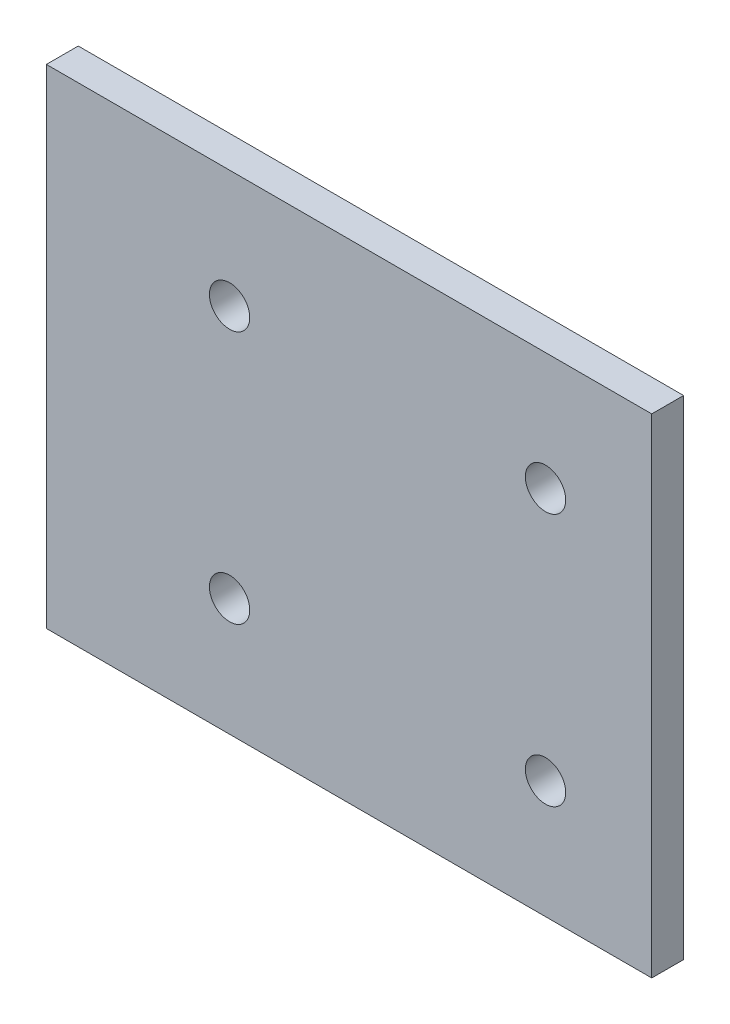
SolidWorks part; units mm, degrees
material "Oak"
ref_plane "Front Plane" through (0, 0, 0) normal (0, 0, 1) x (1, 0, 0)
ref_plane "Top Plane" through (0, 0, 0) normal (0, 1, 0) x (1, 0, 0)
ref_plane "Right Plane" through (0, 0, 0) normal (1, 0, 0) x (0, 0, -1)
sketch "Sketch1" plane through (0, 0, 0) normal (0, 0, 1) x (1, 0, 0)
  line L1 (-36.0143, 24.5902) -> (20.9857, 24.5902)
  line L2 (-36.0143, 24.5902) -> (-36.0143, -21.4098)
  line L3 (-36.0143, -21.4098) -> (20.9857, -21.4098)
  line L4 (20.9857, 24.5902) -> (20.9857, -21.4098)
  dimension "D1" = 46
  dimension "D2" = 57
extrude "Boss-Extrude1" add sketch "Sketch1" along normal blind 3
hole_wizard "#6 Clearance Hole1" positions "Sketch2" profile "Sketch3" hole size "#6" standard "ANSI Inch" end condition through all
sketch "Sketch2" plane through (0, 0, 3) normal (0, 0, 1) x (1, 0, 0)
  line L0 (20.9857, -21.4098) -> (20.9857, 24.5902) construction
  line L1 (20.9857, 24.5902) -> (-36.0143, 24.5902) construction
  line L2 (-36.0143, -21.4098) -> (20.9857, -21.4098) construction
  point P0 (10.9857, 13.5152)
  point P2 (10.9857, -10.3348)
  point P4 (-18.7643, -10.3348)
  point P6 (-18.7643, 13.5152)
  dimension "D1" = 29.75
  dimension "D2" = 29.75
  dimension "D3" = 23.85
  dimension "D4" = 23.85
  dimension "D5" = 10
  dimension "D6" = 11.075
  dimension "D7" = 10
  dimension "D8" = 11.075
sketch "Sketch3" plane through (10.9857, 13.5152, 3) normal (1, 0, 0) x (0, -1, 0)
  line L0 (0, 0) -> (0, 3)
  line L1 (0, 3) -> (1.8986, 3)
  line L2 (1.8986, 3) -> (1.8986, 0)
  line L5 (1.8986, 0) -> (0, 0)
  line L11 (0, -6.35) -> (0, 107.95) construction
  dimension "Thru Hole Dia." = 3.7973
  dimension "Thru Hole Depth" = 3
